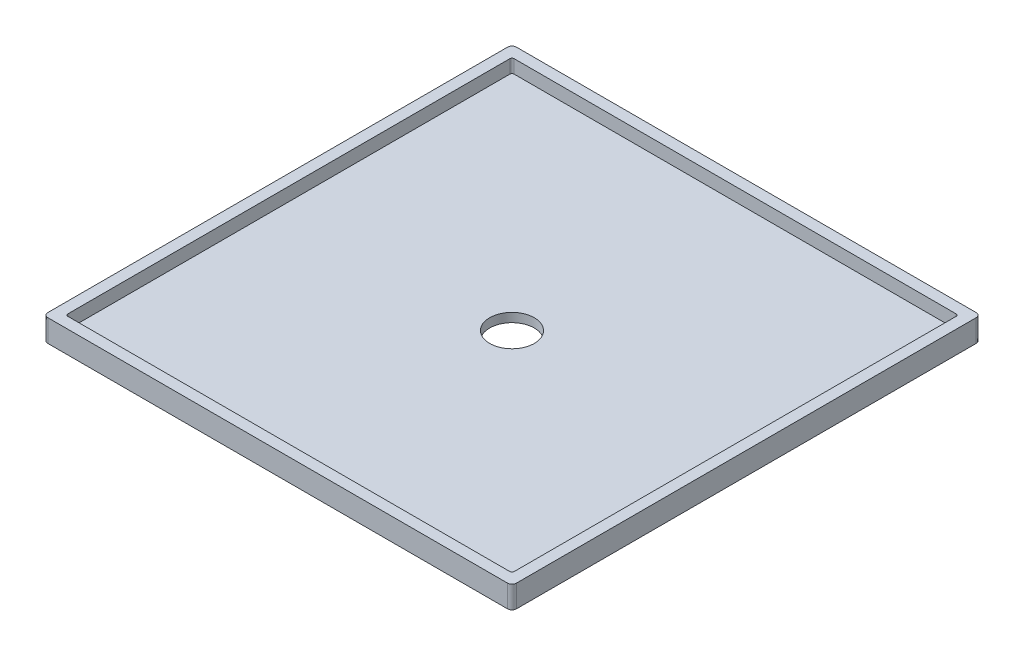
SolidWorks part; units mm, degrees
material "6061 Alloy"
ref_plane "Plano frontal" through (0, 0, 0) normal (0, 0, 1) x (1, 0, 0)
ref_plane "Plano superior" through (0, 0, 0) normal (0, 1, 0) x (1, 0, 0)
ref_plane "Plano direito" through (0, 0, 0) normal (1, 0, 0) x (0, 0, -1)
sketch "Sketch1" plane through (0, 0, 0) normal (0, 1, 0) x (1, 0, 0)
  line L1 (-52.5, -52.5) -> (52.5, -52.5)
  line L2 (-52.5, -52.5) -> (-52.5, 52.5)
  line L3 (-52.5, 52.5) -> (52.5, 52.5)
  line L4 (52.5, -52.5) -> (52.5, 52.5)
  line L5 (-52.5, -52.5) -> (52.5, 52.5) construction
  line L6 (-52.5, 52.5) -> (52.5, -52.5) construction
  dimension "D1" = 105
extrude "Boss-Extrude1" add sketch "Sketch1" along normal blind 5
sketch "Sketch2" plane through (0, 5, 0) normal (0, 1, 0) x (1, 0, 0)
  circle A0 centre (0, 0) radius 5
  dimension "D1" = 10
extrude "Cut-Extrude1" cut sketch "Sketch2" against normal up to surface (5 mm away) up to face at (0, 0, 0)
sketch "Sketch3" plane through (0, 5, 0) normal (0, 1, 0) x (1, 0, 0)
  line L1 (-49.5, -50) -> (49.5, -50)
  line L2 (-50, -49.5) -> (-50, 49.5)
  line L3 (-49.5, 50) -> (49.5, 50)
  line L4 (50, -49.5) -> (50, 49.5)
  line L5 (-50, -50) -> (50, 50) construction
  line L6 (-50, 50) -> (50, -50) construction
  arc A0 (49.5, 50) -> (50, 49.5) centre (49.5, 49.5) cw
  arc A1 (-50, 49.5) -> (-49.5, 50) centre (-49.5, 49.5) cw
  arc A2 (-49.5, -50) -> (-50, -49.5) centre (-49.5, -49.5) cw
  arc A3 (49.5, -50) -> (50, -49.5) centre (49.5, -49.5) ccw
  point P0 (0, 0)
  dimension "D2" = 0.5
  dimension "D1" = 100
extrude "Cut-Extrude2" cut sketch "Sketch3" against normal blind 3
fillet "Fillet1" radius 1 4 edges at (-52.5, 2.5, 52.5) (-52.5, 2.5, -52.5) (52.5, 2.5, -52.5) (52.5, 2.5, 52.5)
